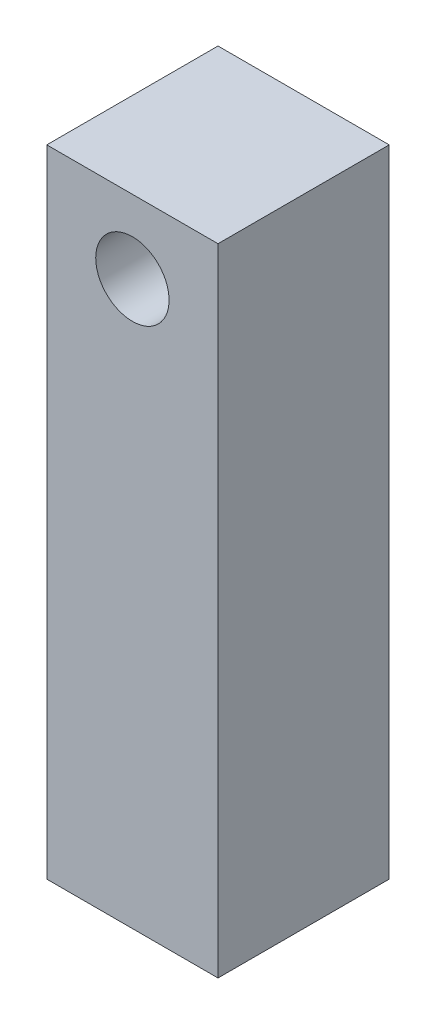
SolidWorks part; units mm, degrees
material "Plain Carbon Steel"
ref_plane "Front Plane" through (0, 0, 0) normal (0, 0, 1) x (1, 0, 0)
ref_plane "Top Plane" through (0, 0, 0) normal (0, 1, 0) x (1, 0, 0)
ref_plane "Right Plane" through (0, 0, 0) normal (1, 0, 0) x (0, 0, -1)
sketch "Sketch1" plane through (0, 0, 0) normal (0, 1, 0) x (1, 0, 0)
  line L1 (-3.5, -3.5) -> (3.5, -3.5)
  line L2 (-3.5, -3.5) -> (-3.5, 3.5)
  line L3 (-3.5, 3.5) -> (3.5, 3.5)
  line L4 (3.5, -3.5) -> (3.5, 3.5)
  line L5 (-3.5, -3.5) -> (3.5, 3.5) construction
  line L6 (-3.5, 3.5) -> (3.5, -3.5) construction
  circle A1 centre (0, 0) radius 2
  dimension "D1" = 7
  dimension "D2" = 4
extrude "Boss-Extrude1" add sketch "Sketch1" along normal blind 20
sketch "Sketch2" plane through (0, 0, 0) normal (0, 0, 1) x (1, 0, 0)
  line L1 (-3.5, 20) -> (3.5, 20) construction
  line L2 (-3.5, 26) -> (3.5, 26)
  line L3 (-3.5, 26) -> (-3.5, 20)
  line L4 (-3.5, 20) -> (3.5, 20)
  line L5 (3.5, 26) -> (3.5, 20)
  line L6 (-3.5, 26) -> (3.5, 20) construction
  line L7 (-3.5, 20) -> (3.5, 26) construction
  line L8 (-3.5, 20) -> (-3.5, 0) construction
  circle A1 centre (0, 23) radius 1.5
  dimension "D1" = 6
  dimension "D2" = 3
extrude "Boss-Extrude2" add sketch "Sketch2" along normal up to surface and the other way up to surface up to face at (0, 10, 3.5) other way up to face at (0, 10, -3.5)
